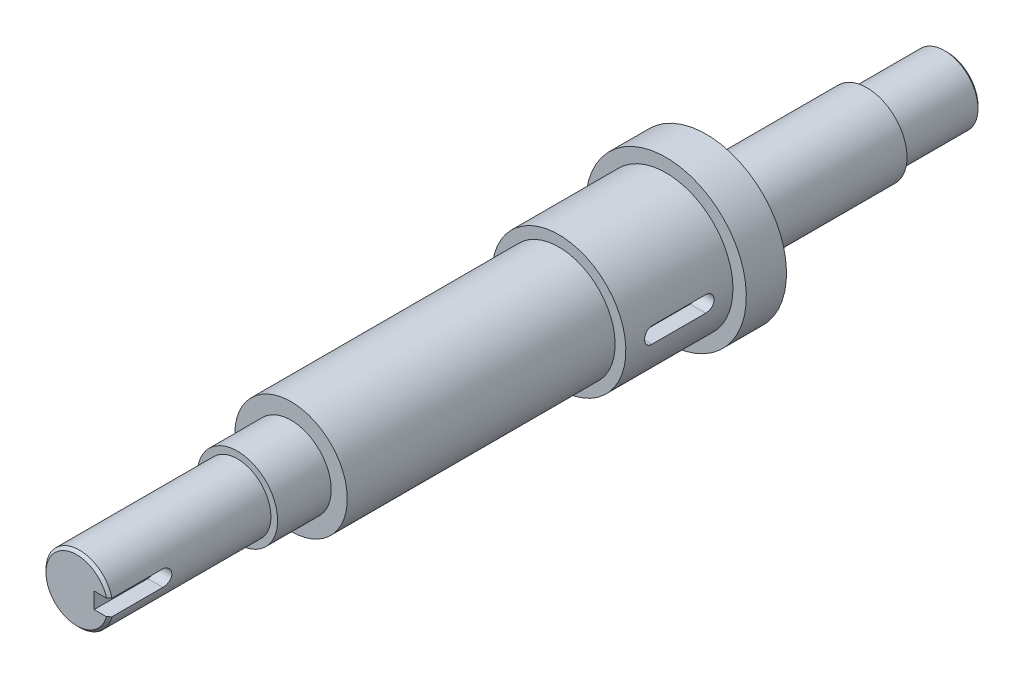
SolidWorks part; units mm, degrees
ref_plane "Front Plane" through (0, 0, 0) normal (0, 0, 1) x (1, 0, 0)
ref_plane "Top Plane" through (0, 0, 0) normal (0, 1, 0) x (1, 0, 0)
ref_plane "Right Plane" through (0, 0, 0) normal (1, 0, 0) x (0, 0, -1)
sketch "Sketch2" plane through (0, 0, 0) normal (1, 0, 0) x (0, 0, -1)
  line L0 (0, 0) -> (-225, 0) construction
  line L1 (-225, 12.5) -> (-225, 0)
  line L2 (-45, 21) -> (-45, 25)
  line L3 (-225, 12.5) -> (-165, 12.5)
  line L4 (-165, 12.5) -> (-165, 15)
  line L5 (-165, 15) -> (-145, 15)
  line L6 (-145, 15) -> (-145, 21)
  line L7 (-145, 21) -> (-45, 21)
  line L8 (-45, 25) -> (-5, 25)
  line L9 (-5, 25) -> (-5, 30)
  line L10 (-5, 30) -> (10, 30)
  line L11 (10, 30) -> (10, 15)
  line L12 (10, 15) -> (70, 15)
  line L13 (70, 15) -> (70, 12.5)
  line L14 (70, 12.5) -> (100, 12.5)
  line L15 (100, 12.5) -> (100, 0)
  line L16 (100, 0) -> (0, 0) construction
  line L17 (-225, 0) -> (100, 0)
  point P15 (-155, 15)
  point P18 (0, 0)
  point P21 (0, 0)
  dimension "D1" = 25
  dimension "D2" = 30
  dimension "D3" = 42
  dimension "D4" = 325
  dimension "D5" = 50
  dimension "D6" = 60
  dimension "D7" = 100
  dimension "D8" = 15
  dimension "D9" = 30
  dimension "D10" = 60
  dimension "D11" = 40
  dimension "D12" = 60
  dimension "D13" = 100
  dimension "D14" = 20
revolve "Revolve1" add sketch "Sketch2" angle 360 about L17
hole_wizard "M8x1.0 Tapped Hole1" positions "3DSketch1" profile "Sketch3" tap size "M8x1.0" standard "ANSI Metric"
sketch3d "3DSketch1"
  line L0 (0, 0, -100) -> (0, 0, -70) construction
  point P0 (0, 0, -100)
sketch "Sketch3" plane through (0, 0, -100) normal (1, 0, 0) x (0, 1, 0)
  line L0 (0, 0) -> (0, 21.103)
  line L1 (0, 21.103) -> (3.5, 19)
  line L2 (3.5, 19) -> (3.5, 0)
  line L5 (3.5, 0) -> (0, 0)
  line L10 (0, 21.103) -> (-3.5, 19) construction
  line L11 (0, -6.35) -> (0, 107.95) construction
  dimension "Tap Drill Dia." = 7
  dimension "Tap Drill Depth" = 19
  dimension "Drill Angle" = 118
cosmetic thread "Hole Thread1" parameters "D1"=16, "D2"=8
ref_plane "Plane1" through (12.5, 0, 0) normal (1, 0, 0) x (0, 0, -1)
sketch "Sketch4" plane through (12.5, 0, 0) normal (1, 0, 0) x (0, 0, -1)
  line L0 (-225, 0) -> (-205, 0) construction
  line L1 (-225, 12.5) -> (-225, -12.5) construction
  line L2 (-205, 3) -> (-225, 3)
  line L3 (-225, 3) -> (-225, -3)
  line L4 (-205, -3) -> (-225, -3)
  arc A0 (-205, -3) -> (-205, 3) centre (-205, 0) ccw
  dimension "D1" = 6
  dimension "D2" = 20
extrude "Cut-Extrude3" cut sketch "Sketch4" against normal blind 6
ref_plane "Plane2" through (25, 0, 0) normal (1, 0, 0) x (0, 0, -1)
sketch "Sketch5" plane through (25, 0, 0) normal (1, 0, 0) x (0, 0, -1)
  line L0 (-5, 25) -> (-5, -25) construction
  line L1 (-15, 0) -> (-5, 0) construction
  line L2 (-35, 0) -> (-45, 0) construction
  line L3 (-35, 0) -> (-15, 0) construction
  line L4 (-35, 3) -> (-15, 3)
  line L5 (-35, -3) -> (-15, -3)
  line L6 (-45, 21) -> (-45, -21) construction
  arc A0 (-35, 3) -> (-35, -3) centre (-35, 0) ccw
  arc A1 (-15, -3) -> (-15, 3) centre (-15, 0) ccw
  point P4 (-25, 0)
  dimension "D1" = 6
  dimension "D2" = 20
  dimension "D3" = 10
extrude "Cut-Extrude4" cut sketch "Sketch5" against normal blind 6
chamfer "Chamfer1" distance 1 angle 45 2 edges at (-12.5, 0, 225) (0, -12.5, -100)
